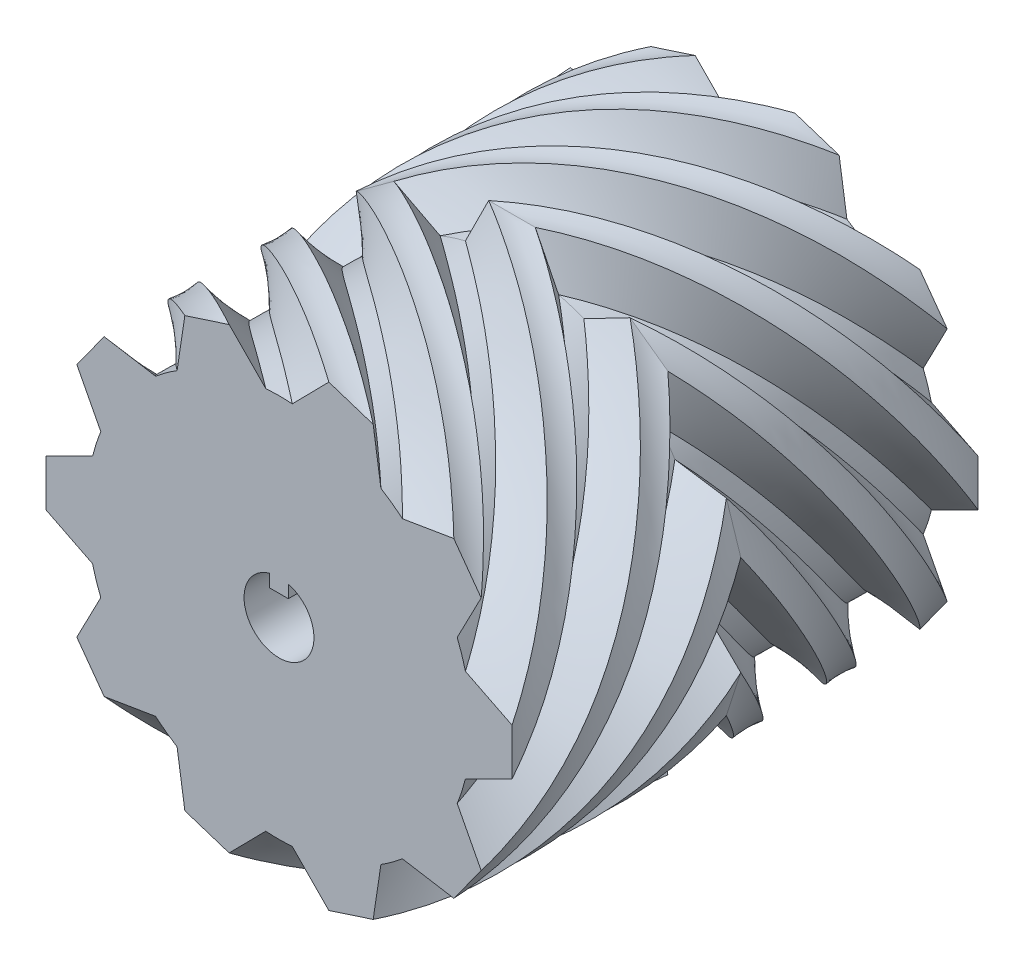
SolidWorks part; units mm, degrees
material "PETG"
ref_plane "Front Plane" through (0, 0, 0) normal (0, 0, 1) x (1, 0, 0)
ref_plane "Top Plane" through (0, 0, 0) normal (0, 1, 0) x (1, 0, 0)
ref_plane "Right Plane" through (0, 0, 0) normal (1, 0, 0) x (0, 0, -1)
sketch "Sketch1" plane through (0, 0, 0) normal (0, 0, 1) x (1, 0, 0)
  line L0 (-0.5, 5) -> (0.5, 5)
  line L1 (-0.5, 5) -> (-1, 4)
  line L2 (0.5, 5) -> (1, 4)
  line L3 (2.5344, 4.339) -> (1.5421, 3.8239)
  line L4 (2.5344, 4.339) -> (3.3434, 3.7512)
  line L5 (3.3434, 3.7512) -> (3.1602, 2.6483)
  line L6 (4.6008, 2.0206) -> (3.4952, 2.1871)
  line L7 (4.6008, 2.0206) -> (4.9098, 1.0696)
  line L8 (4.9098, 1.0696) -> (4.1132, 0.285)
  line L9 (4.9098, -1.0696) -> (4.1132, -0.285)
  line L10 (4.9098, -1.0696) -> (4.6008, -2.0206)
  line L11 (4.6008, -2.0206) -> (3.4952, -2.1871)
  line L12 (3.3434, -3.7512) -> (3.1602, -2.6483)
  line L13 (3.3434, -3.7512) -> (2.5344, -4.339)
  line L14 (2.5344, -4.339) -> (1.5421, -3.8239)
  line L15 (0.5, -5) -> (1, -4)
  line L16 (0.5, -5) -> (-0.5, -5)
  line L17 (-0.5, -5) -> (-1, -4)
  line L18 (-2.5344, -4.339) -> (-1.5421, -3.8239)
  line L19 (-2.5344, -4.339) -> (-3.3434, -3.7512)
  line L20 (-3.3434, -3.7512) -> (-3.1602, -2.6483)
  line L21 (-4.6008, -2.0206) -> (-3.4952, -2.1871)
  line L22 (-4.6008, -2.0206) -> (-4.9098, -1.0696)
  line L23 (-4.9098, -1.0696) -> (-4.1132, -0.285)
  line L24 (-4.9098, 1.0696) -> (-4.1132, 0.285)
  line L25 (-4.9098, 1.0696) -> (-4.6008, 2.0206)
  line L26 (-4.6008, 2.0206) -> (-3.4952, 2.1871)
  line L27 (-3.3434, 3.7512) -> (-3.1602, 2.6483)
  line L28 (-3.3434, 3.7512) -> (-2.5344, 4.339)
  line L29 (-2.5344, 4.339) -> (-1.5421, 3.8239)
  arc A1 (1.5421, 3.8239) -> (1, 4) centre (0, 0) ccw
  arc A2 (3.4952, 2.1871) -> (3.1602, 2.6483) centre (0, 0) ccw
  arc A3 (-1, 4) -> (-1.5421, 3.8239) centre (0, 0) ccw
  arc A4 (1, -4) -> (1.5421, -3.8239) centre (0, 0) ccw
  arc A5 (3.1602, -2.6483) -> (3.4952, -2.1871) centre (0, 0) ccw
  arc A6 (4.1132, -0.285) -> (4.1132, 0.285) centre (0, 0) ccw
  arc A7 (-1.5421, -3.8239) -> (-1, -4) centre (0, 0) ccw
  arc A8 (-3.4952, -2.1871) -> (-3.1602, -2.6483) centre (0, 0) ccw
  arc A9 (-4.1132, 0.285) -> (-4.1132, -0.285) centre (0, 0) ccw
  arc A10 (-3.1602, 2.6483) -> (-3.4952, 2.1871) centre (0, 0) ccw
  dimension "D2" = 1
  dimension "D3" = 0.5
  dimension "D4" = 5
  dimension "D5" = 2
  dimension "D1" = 1
  dimension "D6" = 10
ref_plane "Plane1" through (0, 0, 5) normal (0, 0, 1) x (1, 0, 0)
ref_plane "Plane2" through (0, 0, 10) normal (0, 0, 1) x (1, 0, 0)
sketch "Sketch3" plane through (0, 0, 0) normal (0, 0, 1) x (1, 0, 0)
  circle A0 centre (0, 0) radius 2.5
curve "Helix/Spiral1" pitch 20 height 5 radius 2.5 centre (0, 0, 0) axis (0, 0, -1) start towards (-1, 0, 0)
sweep "Sweep2" add profiles "Sketch1" path "Helix/Spiral1"
mirror "Mirror1" about plane through (0, 0, 0) normal (0, 0, 1) of "Sweep2"
sketch "Sketch4" plane through (0, 0, -5) normal (0, 0, -1) x (-1, 0, 0)
  line L0 (-0.2, 0.45) -> (0.2, 0.45)
  line L1 (0.2, 0.45) -> (0.2, 0.7228)
  line L2 (0, 5.5055) -> (0, -5.5055) construction
  line L3 (-0.2, 0.45) -> (-0.2, 0.7228)
  arc A0 (-0.2, 0.7228) -> (0.2, 0.7228) centre (0, 0) ccw
  point P9 (0, 0.45)
  dimension "D1" = 1.5
  dimension "D2" = 0.2
  dimension "D4" = 0.45
extrude "Cut-Extrude1" cut sketch "Sketch4" against normal through all
equation "\"rail width\"= 50"
equation "\"system width\"= 125"
equation "\"system depth\"= 250"
equation "\"internal height\"= 100"
equation "\"carriage height\"= 50"
equation "\"gear radius\"= 5"
equation "\"tooth width\"= 1"
equation "\"track width\"= 10"
equation "\"D2@Sketch1\"=\"tooth width\""
equation "\"D3@Sketch1\"=\"tooth width\"/2"
equation "\"D4@Sketch1\"=\"gear radius\""
equation "\"D5@Sketch1\"=\"tooth width\" *2"
equation "\"D1@Sketch1\"=1"
